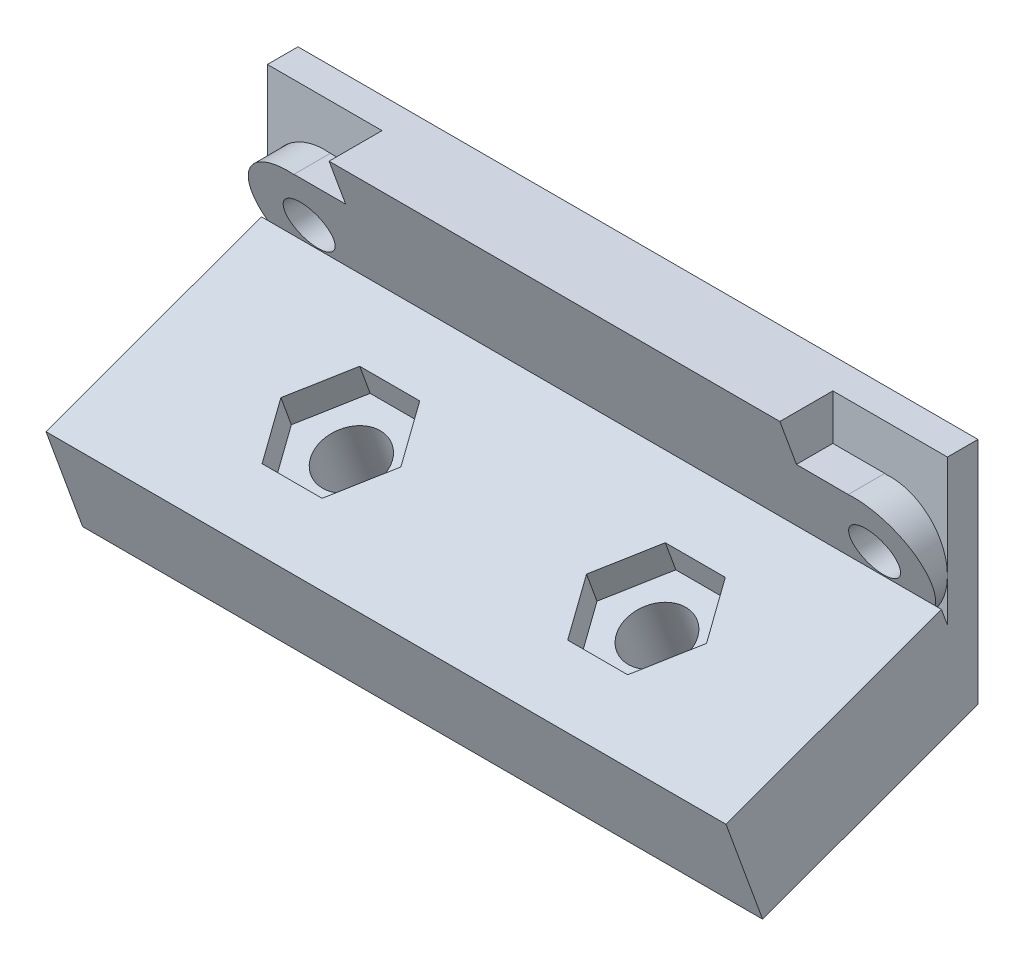
SolidWorks part; units mm, degrees
note: The reader was unsure of these and kept them because the rebuilt part matched: shared geometry of "Sketch2<3>", "Sketch4<2>".
ref_plane "Front Plane" through (0, 0, 0) normal (0, 0, 1) x (1, 0, 0)
ref_plane "Top Plane" through (0, 0, 0) normal (0, 1, 0) x (1, 0, 0)
ref_plane "Right Plane" through (0, 0, 0) normal (1, 0, 0) x (0, 0, -1)
sketch "Sketch2" plane through (0, 0, 0) normal (0, 0, 1) x (1, 0, 0)
  line L0 (0, 2.5231) -> (3.75, 2.5231)
  line L1 (3.38, 10.0048) -> (0, 10.0231)
  line L2 (0, 10.0231) -> (0, 13)
  line L3 (0, 13) -> (-29.5, 13)
  line L4 (-29.5, 13) -> (-29.5, 10.0231)
  line L5 (-29.5, 10.0231) -> (-32.88, 10.0231)
  line L6 (0, 0) -> (0, 2.5231)
  line L7 (0, 0) -> (-29.5, 0)
  line L8 (-29.5, 0) -> (-29.5, 2.5231)
  line L9 (-32.88, 2.5231) -> (-29.5, 2.5231) construction
  line L10 (-29.5, 2.5231) -> (-32.88, 2.5231)
  line L11 (-29.5, 0) -> (-37, 0)
  line L12 (-37, 0) -> (-37, 13)
  line L13 (-37, 13) -> (-29.5, 13)
  line L14 (0, 0) -> (7.5, 0)
  line L15 (7.5, 0) -> (7.5, 13)
  line L16 (7.5, 13) -> (0, 13)
  arc A0 (3.38, 2.5414) -> (3.38, 10.0048) centre (3.75, 6.2731) ccw construction
  arc A1 (-32.88, 10.0231) -> (-32.88, 2.5231) centre (-33.25, 6.2731) ccw
  arc A2 (3.38, 10.0048) -> (3.7252, 2.5232) centre (3.75, 6.2731) cw
  circle A3 centre (3.75, 6.2731) radius 1.6
  circle A4 centre (-33.25, 6.2731) radius 1.6
  arc A5 (-32.88, 10.0048) -> (-32.88, 2.5414) centre (-33.25, 6.2731) ccw construction
  circle M1 centre (-33.25, 6.2731) radius 1.6
  circle M2 centre (3.75, 6.2731) radius 1.6
  arc M3 (3.38, 2.5414) -> (3.38, 10.0048) centre (3.75, 6.2731) ccw
  line M4 (3.38, 10.0048) -> (3.38, 10.0231)
  line M5 (3.38, 10.0231) -> (0, 10.0231)
  line M6 (0, 10.0231) -> (0, 13)
  line M7 (0, 13) -> (-29.5, 13)
  line M8 (-29.5, 13) -> (-29.5, 10.0231)
  line M9 (-29.5, 10.0231) -> (-32.88, 10.0231)
  line M10 (-32.88, 10.0231) -> (-32.88, 10.0048)
  arc M11 (-32.88, 10.0048) -> (-32.88, 2.5414) centre (-33.25, 6.2731) ccw
  line M12 (-32.88, 2.5414) -> (-32.88, 2.5231)
  line M13 (-32.88, 2.5231) -> (-29.5, 2.5231)
  line M14 (-29.5, 2.5231) -> (-29.5, 0)
  line M15 (-29.5, 0) -> (0, 0)
  line M16 (0, 0) -> (0, 2.5231)
  line M17 (0, 2.5231) -> (3.38, 2.5231)
  line M18 (3.38, 2.5231) -> (3.38, 2.5414)
  line M19 (-29, 0.5) -> (-29, 12.5)
  line M20 (-29, 12.5) -> (-0.5, 12.5)
  line M21 (-0.5, 12.5) -> (-0.5, 0.5)
  line M22 (-0.5, 0.5) -> (-29, 0.5)
extrude "Boss-Extrude1" add sketch "Sketch2" along normal blind 2 contours M19 M22 M21 M20 | L15 L16 M6 M5 M4 M3 | L14 L15 L0 M3 M17 M16 | A1 L13 L12 M9 M8 | A1 L12 L11 M14 M13 | L1 M3 M6 M7 M8 M9 M10 M11 M12 M13 M14 M15 M16 M17 M18 M2 M22 M19 M20 M21 M1
sketch "Sketch3" plane through (0, -1.7781, -0.6472) normal (0, 0.9397, 0.342) x (1, 0, 0)
  line L0 (-29.5, -0.6887) -> (20.5, -0.6887) construction
  line L1 (-37, -0.6887) -> (7.5, -0.6887)
  line L2 (-37, -0.6887) -> (-37, -15.6887)
  line L3 (-37, -15.6887) -> (7.5, -15.6887)
  line L4 (7.5, -0.6887) -> (7.5, -15.6887)
  line L5 (-37, -0.6887) -> (7.5, -15.6887) construction
  line L6 (-37, -15.6887) -> (7.5, -0.6887) construction
  line L9 (-37, -1.8794) -> (-37, 0) construction
  line L11 (7.5, -1.8794) -> (7.5, 2.5669) construction
  point P4 (-14.75, -8.1887)
  dimension "D3" = 15
extrude "Boss-Extrude2" add sketch "Sketch3" along normal blind 7
extrude "Boss-Extrude3" add sketch "Sketch2<3>" along normal up to surface (1.6512 mm away) contours M19 M22 M21 M20 | L1 M3 M6 M7 M8 M9 M10 M11 M12 M13 M14 M15 M16 M17 M18 M2 M22 M19 M20 M21 M1
sketch "Sketch2<3>" plane through (0, 0, 0) normal (0, 0, 1) x (1, 0, 0) same geometry as "Sketch2"
sketch "Sketch4" plane through (0, 4.7998, 1.747) normal (0, 0.9397, 0.342) x (1, 0, 0)
  line L0 (-37, -8.1887) -> (7.5, -8.1887) construction
  line L1 (-37, -0.6887) -> (-37, -15.6887) construction
  line L2 (7.5, -15.6887) -> (7.5, -0.6887) construction
  line L5 (-28.676, -8.1887) -> (-26.713, -11.5887)
  line L6 (-26.713, -11.5887) -> (-22.787, -11.5887)
  line L7 (-22.787, -11.5887) -> (-20.824, -8.1887)
  line L8 (-20.824, -8.1887) -> (-22.787, -4.7887)
  line L9 (-22.787, -4.7887) -> (-26.713, -4.7887)
  line L10 (-26.713, -4.7887) -> (-28.676, -8.1887)
  line L11 (-8.676, -8.1887) -> (-6.713, -11.5887)
  line L12 (-6.713, -11.5887) -> (-2.787, -11.5887)
  line L13 (-2.787, -11.5887) -> (-0.824, -8.1887)
  line L14 (-0.824, -8.1887) -> (-2.787, -4.7887)
  line L15 (-2.787, -4.7887) -> (-6.713, -4.7887)
  line L16 (-6.713, -4.7887) -> (-8.676, -8.1887)
  circle A0 centre (-24.75, -8.1887) radius 2.0107
  circle A1 centre (-4.75, -8.1887) radius 2
  circle A2 centre (-24.75, -8.1887) radius 3.4 construction
  circle A3 centre (-4.75, -8.1887) radius 3.4 construction
  dimension "D1" = 4.0215
  dimension "D2" = 4
  dimension "D3" = 20
  dimension "D4" = 12.25
  dimension "D5" = 6.8
  dimension "D6" = 6.8
extrude "Cut-Extrude1" cut sketch "Sketch4" against normal blind 2
extrude "Cut-Extrude2" cut sketch "Sketch4<2>" against normal through all contours A1 | A0
sketch "Sketch4<2>" plane through (0, 4.7998, 1.747) normal (0, 0.9397, 0.342) x (1, 0, 0) same geometry as "Sketch4"
sketch "Sketch5" plane through (7.5, 0, 0) normal (1, 0, 0) x (0, 0, -1)
  line L0 (-0.7329, 0) -> (0, 0)
  line L1 (0, 0) -> (0, -2.0136)
  line L2 (0, -2.0136) -> (-0.7329, 0)
  line L3 (-0.7329, 0) -> (0, -2.0136) construction
extrude "Boss-Extrude4" add sketch "Sketch5" against normal up to surface (44.5 mm away) up to face at (-37, 1.1254, 4.1902)
